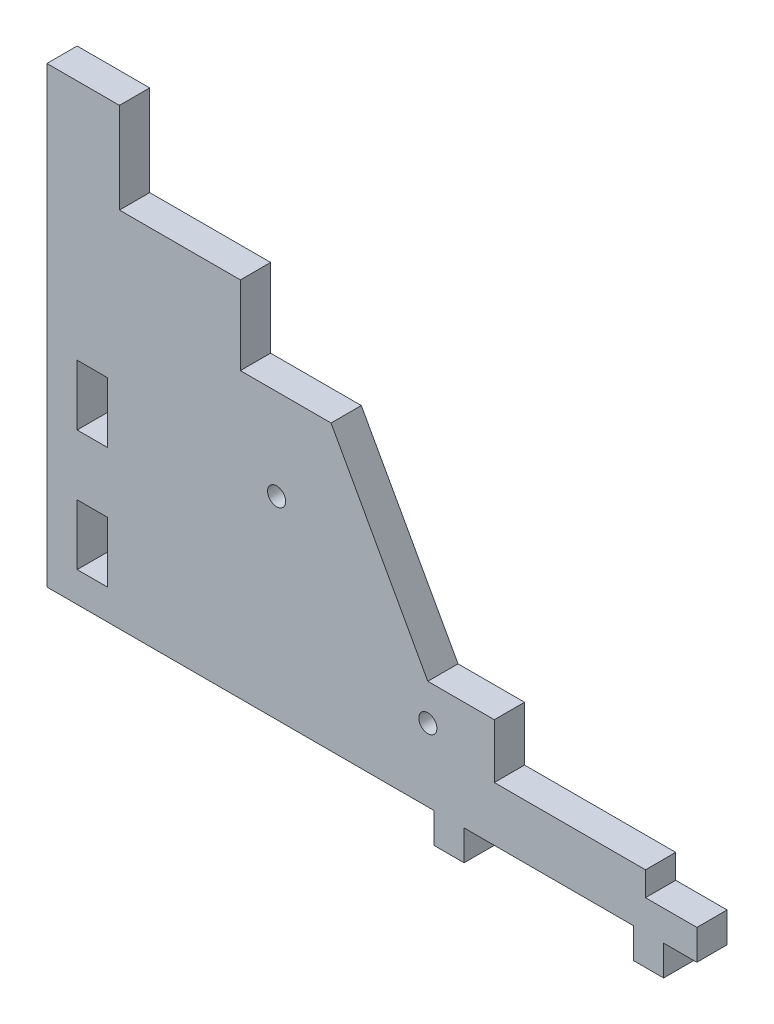
SolidWorks part; units mm, degrees
ref_plane "Plan de face" through (0, 0, 0) normal (0, 0, 1) x (1, 0, 0)
ref_plane "Plan de dessus" through (0, 0, 0) normal (0, 1, 0) x (1, 0, 0)
ref_plane "Plan de droite" through (0, 0, 0) normal (1, 0, 0) x (0, 0, -1)
sketch "Esquisse1" plane through (0, 0, 0) normal (0, 0, 1) x (1, 0, 0)
  line L1 (0, 0) -> (32, 0)
  line L2 (0, 0) -> (0, 47)
  line L3 (0, 47) -> (15, 47)
  line L4 (37, 0) -> (37, 18)
  line L6 (15, 47) -> (31, 18)
  line L7 (31, 18) -> (37, 18)
  line L8 (37, 0) -> (37, -5)
  line L9 (37, -5) -> (32, -5)
  line L10 (32, 0) -> (32, -5)
  circle A0 centre (6, 32) radius 1.5
  circle A1 centre (31, 12) radius 1.5
  dimension "D3" = 20
  dimension "D4" = 3
  dimension "D1" = 6
  dimension "D2" = 12
  dimension "D5" = 15
  dimension "D6" = 6
  dimension "D7" = 25
  dimension "D8" = 15
  dimension "D9" = 6
  dimension "D10" = 5
  dimension "D11" = 5
  dimension "D12" = 6
extrude "Boss.-Extru.1" add sketch "Esquisse1" along normal blind 5
sketch "Esquisse2" plane through (0, 0, 0) normal (0, 0, -1) x (-1, 0, 0)
  line L0 (-37, 18) -> (-31, 18) construction
  line L1 (-37, 0) -> (-65, 0)
  line L2 (-37, 0) -> (-37, 18)
  line L3 (-70, 0) -> (-75.5, 0)
  line L4 (0, 0) -> (32, 0)
  line L5 (0, 20) -> (0, 60)
  line L6 (0, 60) -> (20, 60)
  line L7 (32, 0) -> (32, 75)
  line L8 (0, 0) -> (-32, 0) construction
  line L9 (20, 60) -> (20, 75)
  line L10 (-32, -5) -> (-37, -5) construction
  line L11 (-37, 18) -> (-42, 18)
  line L12 (27, 15) -> (22, 15)
  line L13 (27, 15) -> (27, 5)
  line L14 (27, 5) -> (22, 5)
  line L15 (-70, 0) -> (-70, -5)
  line L16 (-70, -5) -> (-65, -5)
  line L17 (-65, 0) -> (-65, -5)
  line L18 (20, 75) -> (32, 75)
  line L19 (22, 15) -> (22, 5)
  line L20 (27, 35) -> (22, 35)
  line L21 (27, 35) -> (27, 25)
  line L22 (0, 47) -> (0, 0) construction
  line L23 (27, 25) -> (22, 25)
  line L24 (22, 35) -> (22, 25)
  line L25 (-37, 18) -> (-37, 8.7186)
  line L26 (0, 0) -> (-32, 0) construction
  line L27 (-75.5, 5) -> (-67, 5)
  line L28 (-42, 18) -> (-42, 9)
  line L29 (-37, -5) -> (-37, 18) construction
  line L31 (-75.5, 0) -> (-75.5, 5)
  line L32 (-67, 9) -> (-42, 9)
  line L34 (-67, 5) -> (-67, 9)
  circle A0 centre (-31, 12) radius 1.5 construction
  line M2 (0, 0) -> (0, 47)
  line M6 (-37, 18) -> (-37, -5)
  dimension "D1" = 38.5
  dimension "D2" = 20
  dimension "D3" = 28
  dimension "D4" = 5
  dimension "D5" = 10
  dimension "D6" = 5
  dimension "D7" = 15
  dimension "D8" = 10
  dimension "D9" = 5
  dimension "D10" = 32
  dimension "D11" = 11
  dimension "D12" = 5
  dimension "D13" = 60
  dimension "D14" = 25
  dimension "D15" = 40
  dimension "D16" = 5
  dimension "D17" = 3
extrude "Boss.-Extru.2" add sketch "Esquisse2" against normal blind 5 contours L18 L9 L6 L5 L4 M2 | L1 M6 region at (53.6814, 4.8791, 0) region at (-16.475, 33.875, 0)
